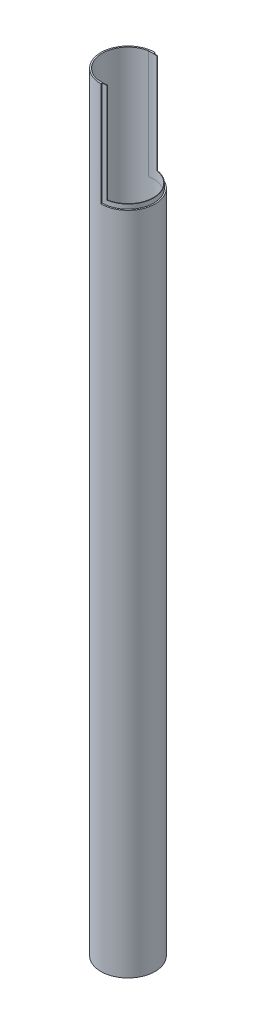
SolidWorks part; units mm, degrees
ref_plane "Front Plane" through (0, 0, 0) normal (0, 0, 1) x (1, 0, 0)
ref_plane "Top Plane" through (0, 0, 0) normal (0, 1, 0) x (1, 0, 0)
ref_plane "Right Plane" through (0, 0, 0) normal (1, 0, 0) x (0, 0, -1)
sketch "Sketch1" plane through (0, 0, 0) normal (0, 1, 0) x (1, 0, 0)
  circle A0 centre (0, 0) radius 60
  circle A1 centre (0, 0) radius 57
  dimension "D1" = 3
extrude "Boss-Extrude1" add sketch "Sketch1" along normal blind 1700
sketch "Sketch4" plane through (0, 0, 0) normal (0, -1, 0) x (1, 0, 0)
  circle A0 centre (0, 0) radius 49
extrude "Boss-Extrude2" add sketch "Sketch4" against normal blind 1239 separate body contours A0
sketch "Sketch7" plane through (0, 0, 0) normal (0, 0, 1) x (1, 0, 0)
  line L0 (60, 1700) -> (-60, 1700) construction
  line L1 (0, 1700) -> (139.9118, 1700)
  line L2 (0, 1700) -> (0, 1470)
  line L3 (0, 1470) -> (139.9118, 1470)
  line L4 (139.9118, 1700) -> (139.9118, 1470)
  point P6 (139.9118, 1479.1651)
  dimension "D1" = 230
extrude "Cut-Extrude1" cut sketch "Sketch7" against normal blind 1239 and the other way blind 1239
sketch "Sketch8" plane through (0, 1470, 0) normal (0, 1, 0) x (1, 0, 0)
  line L2 (-9.7243, -55.1492) -> (-9.8979, -56.134)
  line L3 (-9.7243, 55.1492) -> (-9.8979, 56.134)
  arc A0 (-9.8979, -56.134) -> (-9.8979, 56.134) centre (0, 0) ccw
  arc A2 (-9.7243, -55.1492) -> (-9.7243, 55.1492) centre (0, 0) ccw
  circle A3 centre (0, 0) radius 57 construction
  circle A4 centre (0, 0) radius 56 construction
  dimension "D1" = 1
extrude "Boss-Extrude5" add sketch "Sketch8" along normal blind 10 and the other way blind 10
sketch "Sketch9" plane through (0, 1480, 0) normal (0, 1, 0) x (1, 0, 0)
  line L1 (-9.8979, -56.134) -> (-9.7243, -55.1492)
  line L2 (8.8067, 56.3156) -> (8.6522, 55.3276)
  line L3 (9.8979, -56.134) -> (9.7243, -55.1492)
  line L4 (-9.8979, 56.134) -> (-9.7243, 55.1492)
  arc A0 (8.6522, 55.3276) -> (-9.7243, 55.1492) centre (0, 0) ccw
  arc A1 (8.8067, 56.3156) -> (-9.8979, 56.134) centre (0, 0) ccw
  arc A2 (-9.7243, -55.1492) -> (9.7243, -55.1492) centre (0, 0) ccw
  arc A3 (-9.8979, -56.134) -> (9.8979, -56.134) centre (0, 0) ccw
  dimension "D1" = 20
extrude "Boss-Extrude6" add sketch "Sketch9" along normal blind 220
